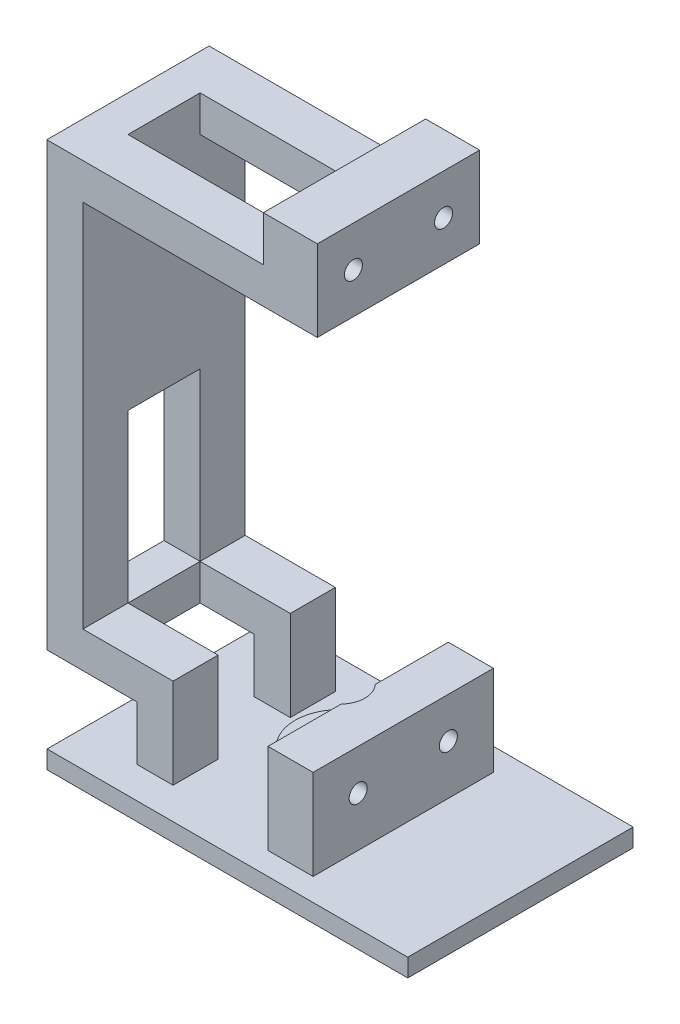
SolidWorks part; units mm, degrees
ref_plane "Front Plane" through (0, 0, 0) normal (0, 0, 1) x (1, 0, 0)
ref_plane "Top Plane" through (0, 0, 0) normal (0, 1, 0) x (1, 0, 0)
ref_plane "Right Plane" through (0, 0, 0) normal (1, 0, 0) x (0, 0, -1)
sketch "Sketch1" plane through (0, 0, 0) normal (0, 1, 0) x (1, 0, 0)
  line L0 (-20, 0) -> (20, 0) construction
  line L1 (-20, -12.5) -> (20, -12.5)
  line L2 (-20, -12.5) -> (-20, 12.5)
  line L3 (-20, 12.5) -> (20, 12.5)
  line L4 (20, -12.5) -> (20, 12.5)
  line L5 (-20, -12.5) -> (20, 12.5) construction
  line L6 (-20, 12.5) -> (20, -12.5) construction
  line L7 (0, 12.5) -> (0, -12.5) construction
  line L8 (-7.9106, 3.9553) -> (7.0894, 3.9553)
  line L9 (-7.9106, 3.9553) -> (-7.9106, -3.5447)
  line L10 (-7.9106, -3.5447) -> (7.0894, -3.5447)
  line L11 (7.0894, 3.9553) -> (7.0894, -3.5447)
  line L12 (-7.9106, 3.9553) -> (7.0894, -3.5447) construction
  line L13 (-7.9106, -3.5447) -> (7.0894, 3.9553) construction
  circle A0 centre (0, 7.9553) radius 1
  circle A1 centre (0, -7.5447) radius 1
  circle A2 centre (16, 0) radius 1
  circle A3 centre (-16, 0) radius 1
  point P0 (0, 0)
  point P8 (0, 0)
  dimension "D5" = 2
  dimension "D7" = 2
  dimension "D9" = 2
  dimension "D1" = 40
  dimension "D2" = 25
  dimension "D3" = 15
  dimension "D4" = 7.5
  dimension "D6" = 4
  dimension "D8" = 4
  dimension "D10" = 16
extrude "Boss-Extrude1" add sketch "Sketch1" along normal blind 2 contours L2 L1 L4 L3
sketch "Sketch2" plane through (0, 2, 0) normal (0, 1, 0) x (1, 0, 0)
  line L1 (2, 10) -> (7, 10)
  line L2 (2, 10) -> (2, -10)
  line L3 (2, -10) -> (7, -10)
  line L4 (7, 10) -> (7, -10)
  line L5 (20, -12.5) -> (20, 12.5) construction
  point P6 (20, 0)
  point P7 (7, 0)
  dimension "D1" = 20
  dimension "D2" = 13
  dimension "D3" = 5
extrude "Boss-Extrude2" add sketch "Sketch2" along normal blind 10
sketch "Sketch4" plane through (7, 0, 0) normal (1, 0, 0) x (0, 0, -1)
  line L0 (-7.046, 10.16) -> (2.954, 10.16) construction
  line L3 (-10, 12) -> (9.965, 12)
  line L4 (-10, 12) -> (-10, 6)
  line L5 (-10, 6) -> (9.965, 6)
  line L6 (9.965, 12) -> (9.965, 6)
  dimension "D1" = 10
  dimension "D2" = 6
extrude "Boss-Extrude3" add sketch "Sketch4" against normal up to surface (5 mm away) up to face at (2, 7, 0)
sketch "Sketch5" plane through (7, 0, 0) normal (1, 0, 0) x (0, 0, -1)
  line L0 (-5, 7.5) -> (5, 7.5) construction
  line L1 (-10, 12) -> (10, 12) construction
  circle A0 centre (5, 7.5) radius 1
  circle A1 centre (-5, 7.5) radius 1
  point P4 (0, 12)
  point P5 (0, 7.5)
  dimension "D2" = 2
  dimension "D3" = 2
  dimension "D1" = 10
  dimension "D4" = 4.5
extrude "Cut-Extrude2" cut sketch "Sketch5" against normal up to surface (5 mm away) up to face at (2, 7, 0)
sketch "Sketch6" plane through (0, 2, 0) normal (0, 1, 0) x (1, 0, 0)
  line L0 (-20, 12.5) -> (-20, -12.5) construction
  line L1 (-13.5277, 9) -> (-9.5277, 9)
  line L2 (-13.5277, 9) -> (-13.5277, -9)
  line L3 (-13.5277, -9) -> (-9.5277, -9)
  line L4 (-9.5277, 9) -> (-9.5277, -9)
  line L10 (-13.5277, 4) -> (-9.5277, 4)
  line L11 (-13.5277, 4) -> (-13.5277, -4)
  line L12 (-13.5277, -4) -> (-9.5277, -4)
  line L13 (-9.5277, 4) -> (-9.5277, -4)
  point P6 (-20, 0)
  point P7 (-13.5277, 0)
  point P12 (-13.5277, 0)
  dimension "D1" = 4
  dimension "D2" = 18
  dimension "D3" = 4
  dimension "D4" = 8
extrude "Boss-Extrude4" add sketch "Sketch6" along normal blind 10 contours L12 L2 L3 L4 | L2 L10 L4 L1 region at (-11.5277, 2, -6.5) region at (-11.5277, 2, 6.5)
sketch "Sketch8" plane through (-13.5277, 0, 0) normal (-1, 0, 0) x (0, 0, 1)
  line L1 (-9, 12) -> (-4, 12)
  line L2 (-9, 12) -> (-9, 8)
  line L3 (-9, 8) -> (-4, 8)
  line L4 (-4, 12) -> (-4, 8)
  dimension "D1" = 5
  dimension "D2" = 4
ref_plane "Plane1" through (0, 0, 0) normal (0, 0, -1) x (-1, 0, 0)
extrude "Boss-Extrude5" add sketch "Sketch8" along normal blind 10
mirror "Mirror1" about plane through (0, 0, 0) normal (0, 0, -1) of "Boss-Extrude5"
sketch "Sketch9" plane through (0, 12, 0) normal (0, 1, 0) x (1, 0, 0)
  line L0 (-23.5277, 4) -> (-9.5277, 4) construction
  line L1 (-23.5277, 9) -> (-19.5277, 9)
  line L2 (-23.5277, 9) -> (-23.5277, 4)
  line L3 (-23.5277, 4) -> (-19.5277, 4)
  line L4 (-19.5277, 9) -> (-19.5277, 4)
  dimension "D1" = 4
  dimension "D2" = 0
extrude "Boss-Extrude6" add sketch "Sketch9" along normal blind 45
mirror "Mirror2" about plane through (0, 0, 0) normal (0, 0, -1) of "Boss-Extrude5"
mirror "Mirror3" about plane through (0, 0, 0) normal (0, 0, -1) of "Boss-Extrude6"
sketch "Sketch12" plane through (-23.5277, 0, 0) normal (-1, 0, 0) x (0, 0, 1)
  line L0 (9, 57) -> (9, 8) construction
  line L1 (-9, 57) -> (9, 57)
  line L2 (-9, 57) -> (-9, 53)
  line L3 (-9, 53) -> (9, 53)
  line L4 (9, 57) -> (9, 53)
  line L5 (-10, 12) -> (10, 12) construction
  line L6 (-9, 8) -> (9, 8)
  line L7 (-9, 8) -> (-9, 12)
  line L8 (-9, 12) -> (9, 12)
  line L9 (9, 8) -> (9, 12)
  line L10 (-9, 32.5) -> (9, 32.5) construction
  line L11 (-9, 57) -> (-9, 8) construction
  line L13 (-9, 30.5) -> (9, 30.5)
  line L14 (-9, 30.5) -> (-9, 34.5)
  line L15 (-9, 34.5) -> (9, 34.5)
  line L16 (9, 30.5) -> (9, 34.5)
  line L17 (-9, 30.5) -> (9, 34.5) construction
  line L18 (-9, 34.5) -> (9, 30.5) construction
  point P18 (0, 32.5)
  dimension "D1" = 4
  dimension "D2" = 4
  dimension "D3" = 4
extrude "Boss-Extrude8" add sketch "Sketch12" against normal up to surface (4 mm away) up to face at (-19.5277, 34.5, 6.5)
sketch "Sketch13" plane through (-19.5277, 0, 0) normal (1, 0, 0) x (0, 0, -1)
  line L1 (-9, 57) -> (-4, 57)
  line L2 (-9, 57) -> (-9, 53)
  line L3 (-9, 53) -> (-4, 53)
  line L4 (-4, 57) -> (-4, 53)
  line L5 (9, 57) -> (4, 57)
  line L6 (9, 57) -> (9, 53)
  line L7 (9, 53) -> (4, 53)
  line L8 (4, 57) -> (4, 53)
extrude "Boss-Extrude9" add sketch "Sketch13" along normal blind 26
sketch "Sketch14" plane through (6.4723, 0, 0) normal (1, 0, 0) x (0, 0, -1)
  line L0 (-9, 57) -> (9, 57)
  line L1 (-9, 57) -> (-9, 53)
  line L2 (9, 57) -> (9, 53)
  line L3 (-9, 53) -> (9, 53)
  line L4 (-9, 53) -> (-4, 53) construction
extrude "Boss-Extrude10" add sketch "Sketch14" against normal blind 6
sketch "Sketch15" plane through (6.4723, 0, 0) normal (1, 0, 0) x (0, 0, -1)
  line L0 (-5, 57.5) -> (5, 57.5) construction
  line L1 (-9, 53) -> (9, 53) construction
  line L2 (-5, 7.5) -> (-5, 57.5) construction
  circle A0 centre (-5, 57.5) radius 1
  circle A1 centre (5, 57.5) radius 1
  dimension "D3" = 2
  dimension "D4" = 2
  dimension "D1" = 10
  dimension "D2" = 4.5
sketch "Sketch16" plane through (0, 57, 0) normal (0, 1, 0) x (1, 0, 0)
  line L0 (6.4723, 9) -> (6.4723, -9)
  line L1 (6.4723, 9) -> (0.4841, 9)
  line L2 (6.4723, -9) -> (0.4841, -9)
  line L3 (0.4841, 9) -> (0.4841, -9)
extrude "Boss-Extrude11" add sketch "Sketch16" along normal blind 5
extrude "Cut-Extrude3" cut sketch "Sketch15" against normal blind 6
sketch "Sketch17" plane through (0, 0, 0) normal (0, -1, 0) x (1, 0, 0)
  circle A0 centre (0, 0) radius 3
  circle A1 centre (0, 0) radius 5
  dimension "D1" = 6
  dimension "D2" = 2
sketch "Sketch18" plane through (-23.5277, 0, 0) normal (-1, 0, 0) x (0, 0, 1)
  line L0 (0, 0) -> (0, 62) construction
  line L1 (-9, 62) -> (9, 62) construction
  line L2 (-17.0412, 42) -> (24.329, 42) construction
  line L3 (12.5, 0) -> (-12.5, 0) construction
  dimension "42" = 42
extrude "Cut-Extrude5" cut sketch "Sketch17" against normal blind 6 contours A0
ref_plane "Plane2" through (0, 1, 0) normal (0, -1, 0) x (-1, 0, 0)
ref_plane "Plane3" through (0, 3, 0) normal (0, 1, 0) x (1, 0, 0)
sketch "Sketch20" plane through (0, 3, 0) normal (0, 1, 0) x (1, 0, 0)
  circle A0 centre (0, 0) radius 3
  circle A1 centre (0, 0) radius 5
  dimension "D1" = 6
  dimension "D2" = 2
sketch "Sketch23" plane through (20, 0, 0) normal (1, 0, 0) x (0, 0, -1)
  line L0 (-12.5, 2) -> (-10.5, 2)
  line L1 (-12.5, 2) -> (-12.5, 59.5)
  line L2 (12.5, 2) -> (12.5, 59.5)
  line L3 (-10.5, 2) -> (-10.5, 59.5)
  line L4 (-12.5, 2) -> (12.5, 2) construction
  line L5 (10.5, 2) -> (10.5, 59.5)
  line L6 (10.5, 2) -> (12.5, 2)
  arc A0 (12.5, 59.5) -> (-12.5, 59.5) centre (0, 59.5) ccw
  arc A1 (10.5, 59.5) -> (-10.5, 59.5) centre (0, 59.5) ccw
  dimension "D2" = 2
sketch "Sketch24" plane through (-23.5277, 0, 0) normal (-1, 0, 0) x (0, 0, 1)
  line L2 (4, 34.5) -> (4, 53) construction
  line L3 (-4, 34.5) -> (4, 34.5)
  line L4 (-4, 34.5) -> (-4, 53)
  line L5 (-4, 53) -> (4, 53)
  line L6 (4, 34.5) -> (4, 53)
  line L7 (-4, 34.5) -> (4, 53) construction
  line L8 (-4, 53) -> (4, 34.5) construction
  line L9 (4, 34.5) -> (-4, 34.5) construction
  line M1 (4, 53) -> (4, 34.5)
  line M3 (-4, 34.5) -> (-4, 53)
extrude "Boss-Extrude18" add sketch "Sketch24" against normal blind 4 contours L5 L3 M3 | L3 L5 M1 region at (-23.5277, 43.75, 0)
extrude "Boss-Extrude20" add sketch "Sketch20" against normal blind 1
sketch "Sketch26" plane through (0, 3, 0) normal (0, 1, 0) x (1, 0, 0)
  circle A0 centre (0, 0) radius 2.9983
  circle A1 centre (0, 0) radius 5
  circle A2 centre (0, 0) radius 1.5
  line M1 (2, -4.5826) -> (2, -2.2361)
  arc M2 (2, -2.2361) -> (2, 2.2361) centre (0, 0) cw
  line M3 (2, 2.2361) -> (2, 4.5826)
  arc M4 (2, 4.5826) -> (2, -4.5826) centre (0, 0) ccw
  dimension "D1" = 3
extrude "Boss-Extrude21" add sketch "Sketch26" along normal blind 1 contours A0 A2 | M4 M1 M2 M3 region at (-2.9135, 3, 0) region at (1.8779, 3, -3.4093)
sketch "Sketch27" plane through (0, 4, 0) normal (0, 1, 0) x (1, 0, 0)
  circle A0 centre (0, 0) radius 5
  circle A1 centre (0, 0) radius 2.75
  dimension "D1" = 5.5
extrude "Boss-Extrude22" add sketch "Sketch27" along normal blind 2
sketch "Sketch28" plane through (0, 6, 0) normal (0, 1, 0) x (1, 0, 0)
  circle A0 centre (0, 0) radius 2.75
extrude "Cut-Extrude10" cut sketch "Sketch28" along normal blind 10
sketch "Sketch29" plane through (-23.5277, 0, 0) normal (-1, 0, 0) x (0, 0, 1)
  circle A0 centre (-0.05, 43.4) radius 4
  dimension "D1" = 8
extrude "Boss-Extrude23" add sketch "Sketch29" along normal blind 5
sketch "Sketch30" plane through (-23.5277, 0, 0) normal (-1, 0, 0) x (0, 0, 1)
  line L0 (-9, 32.5) -> (9, 32.5) construction
  line L1 (-9, 57) -> (-9, 8) construction
  line L2 (9, 57) -> (9, 8) construction
  line L3 (0, 57) -> (0, 8) construction
  line L4 (-9, 57) -> (9, 57) construction
  line L5 (-9, 8) -> (9, 8) construction
equation "\"inner-diameter\"= 10mm"
equation "\"outer-diameter\"= 20mm"
